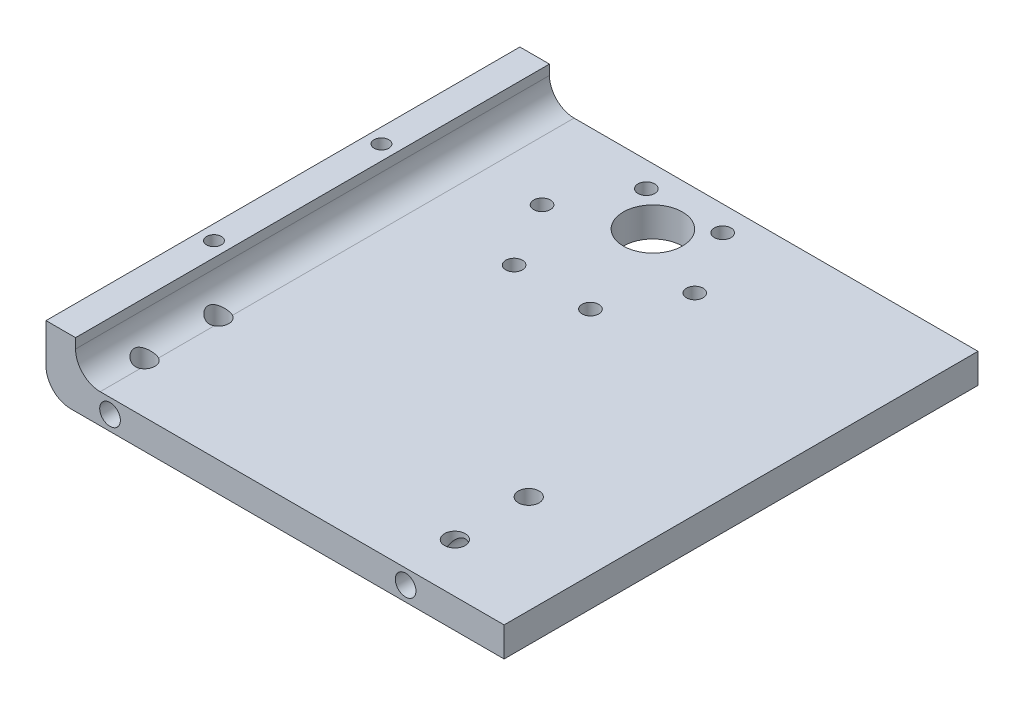
SolidWorks part; units mm, degrees
ref_plane "Front Plane" through (0, 0, 0) normal (1, 0, 0) x (0, 1, 0)
ref_plane "Top Plane" through (0, 0, 0) normal (0, 0, 1) x (0, 1, 0)
ref_plane "Right Plane" through (0, 0, 0) normal (0, 1, 0) x (-1, 0, 0)
sketch "Sketch1" plane through (0, 0, 0) normal (0, 1, 0) x (-1, 0, 0)
  line L0 (-49.4324, 0) -> (-18.4787, 0) construction
  line L1 (0, 0) -> (93, 0)
  line L2 (0, 0) -> (0, 96.2019)
  line L3 (0, 96.2019) -> (93, 96.2019)
  line L4 (93, 0) -> (93, 96.2019)
  line L5 (54.5, -5.8421) -> (54.5, -110.2871) construction
  line L6 (73, -5.0508) -> (73, 63.3751) construction
  line L8 (20, 86.2019) -> (83, 86.2019) construction
  line L9 (20, 86.2019) -> (20, 71.2019) construction
  line L10 (20, 71.2019) -> (83, 71.2019) construction
  line L11 (83, 86.2019) -> (83, 71.2019) construction
  circle A1 centre (54.5, 11.5) radius 6
  circle A2 centre (54.5, 18.5) radius 18.5 construction
  circle A3 centre (54.5, 18.5) radius 15.5 construction
  circle A4 centre (39, 18.5) radius 1.7
  circle A5 centre (46.75, 31.9234) radius 1.7
  circle A6 centre (62.25, 31.9234) radius 1.7
  circle A7 centre (70, 18.5) radius 1.7
  circle A8 centre (62.25, 5.0766) radius 1.7
  circle A9 centre (46.75, 5.0766) radius 1.7
  circle A12 centre (20, 86.2019) radius 2.1
  circle A13 centre (83, 86.2019) radius 2.1
  circle A14 centre (83, 71.2019) radius 2.1
  circle A15 centre (20, 71.2019) radius 2.1
  point P33 (93, 96.2019)
  dimension "D4" = 37
  dimension "D5" = 31
  dimension "D6" = 3.4
  dimension "D7" = 12
  dimension "D11" = 4.2
  dimension "D1" = 96.2019
  dimension "D2" = 93
  dimension "D8" = 7
  dimension "D9" = 20
  dimension "D12" = 10
  dimension "D13" = 20
  dimension "D14" = 10
  dimension "D15" = 15
  dimension "D3" = 6
extrude "Boss-Extrude1" add sketch "Sketch1" along normal blind 6
sketch "Sketch2" plane through (0, 0, 0) normal (0, -1, 0) x (-1, 0, 0)
  line L0 (90, -31.101) -> (90, -65.1009) construction
  line L1 (93, 0) -> (93, -96.2019) construction
  line L2 (93, 0) -> (93, -96.2019)
  line L3 (93, 0) -> (87, 0)
  line L4 (0, 0) -> (93, 0) construction
  line L5 (87, 0) -> (87, -96.2019)
  line L6 (93, -96.2019) -> (0, -96.2019) construction
  line L7 (87, -96.2019) -> (93, -96.2019)
  line L8 (93, -48.1009) -> (87, -48.1009) construction
  circle A0 centre (90, -65.1009) radius 1.5
  circle A1 centre (90, -31.101) radius 1.5
  point P19 (90, -48.1009)
  dimension "D3" = 6
  dimension "D1" = 3
  dimension "D2" = 34
extrude "Boss-Extrude2" add sketch "Sketch2" against normal blind 7 from surface starting at face at (-46.5, 6, 48.1009)
extrude "Cut-Extrude2" cut sketch "Sketch2<3>" against normal through all contours A1 | A0 region at (-90, 0, 65.1009) region at (-90, 0, 31.101)
sketch "Sketch2<3>" plane through (0, 0, 0) normal (0, -1, 0) x (-1, 0, 0) same geometry as "Sketch2"
sketch "Sketch3" plane through (0, 0, 0) normal (0, 0, -1) x (1, 0, 0)
  line L0 (-46.5, 0) -> (-46.5, -6) construction
  line L1 (-80, -3) -> (-20, -3) construction
  line L2 (0, 0) -> (-93, 0) construction
  line L3 (0, -6) -> (-87, -6) construction
  line L4 (0, -6) -> (0, 0) construction
  circle A0 centre (-80, -3) radius 2.1
  circle A1 centre (-20, -3) radius 2.1
  point P6 (-46.5, -3)
  dimension "D1" = 4.2
  dimension "D3" = 20
  dimension "D2" = 60
extrude "Cut-Extrude3" cut sketch "Sketch3" against normal blind 18
extrude "Cut-Extrude4" cut sketch "Sketch3<2>" along normal blind 18 from surface starting at face at (-60, 6.3333, 96.2019)
sketch "Sketch3<2>" plane through (0, 0, 0) normal (0, 0, -1) x (1, 0, 0) same geometry as "Sketch3"
fillet "Fillet1" radius 5 2 edges at (-93, 0, 48.1009) (-87, 6, 48.1009)
equation "\"MotorDriverLength\"= 60mm"
equation "\"MotorLength\"= 60"
equation "\"MotorDriverWidth\"=44"
equation "\"MotorWidth\"= 37"
equation "\"InnerWallThickness\"=3"
equation "\"BatteryWidth\"= 60"
equation "\"OuterWallThickness\" = 6"
equation "\"CompartmentHeight\"=37"
equation "\"CompartmentWidth\"= \"MotorDriverLength\""
equation "\"MotorDiameter\"=37"
equation "\"BatteryHeight\"=24.2019"
equation "\"MotorDriverHeight\"=28"
equation "\"CircuitHeight\"=30"
equation "\"FanThickness\"= 10"
equation "\"FanHeight\"=50"
equation "\"MotorShaftHole\"=12"
equation "\"BearingBore\"=10"
equation "\"MinShinWidth\"= 20"
equation "\"ShinThickness\"=10"
equation "\"PivotDistance\"=30"
equation "\"ThighLength\"= 150"
equation "\"KneeLength\" =80"
equation "\"HipBore\"=27"
equation "\"ThighThickness\"=10"
equation "\"MaxBending\"=135"
equation "\"MaxStretchingAngle\"= 50"
equation "\"ThighJointDistance\"=157.485"
equation "\"ShinLength\"=120"
equation "\"BearingDiameter\"= 10"
equation "\"CircuitLength\"=50"
equation "\"ChessisInnerWidth\"= \"OuterWallThickness\" * 2 + \"MotorDriverLength\" + \"MotorDiameter\" + \"InnerWallThickness\" * 3 + \"CircuitLength\""
equation "\"ChessisHeight\"= \"BatteryHeight\" + 10 + \"InnerWallThickness\" + \"MotorDiameter\" + 10 + \"OuterWallThickness\" * 2"
equation "\"ChassisWidth\"= \"MotorDriverWidth\"*4+30"
equation "\"D1@Sketch1\"=\"ChessisHeight\""
equation "\"D2@Sketch1\"=\"MotorWidth\"+\"FanThickness\"*2 +\"OuterWallThickness\"+30"
equation "\"D9@Sketch1\"=\"FanThickness\"*2"
equation "\"D1@Boss-Extrude1\"=\"OuterWallThickness\""
equation "\"D1@Boss-Extrude2\"=\"OuterWallThickness\"+1"
equation "\"D2@Sketch2\"=17*2"
